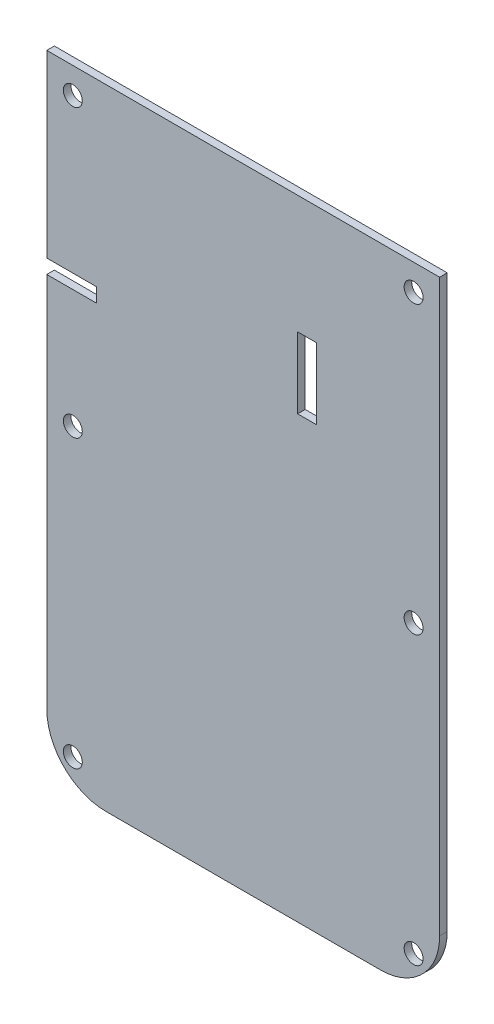
SolidWorks part; units mm, degrees
ref_plane "前视基准面" through (0, 0, 0) normal (0, 0, 1) x (1, 0, 0)
ref_plane "上视基准面" through (0, 0, 0) normal (0, 1, 0) x (1, 0, 0)
ref_plane "右视基准面" through (0, 0, 0) normal (1, 0, 0) x (0, 0, -1)
sketch "草图1" plane through (0, 0, 0) normal (0, 0, 1) x (1, 0, 0)
  line L1 (-41.5, 66.5) -> (0, 66.5)
  line L2 (-41.5, 66.5) -> (-41.5, 6.25)
  line L3 (-35.25, 0) -> (-6.25, 0)
  line L4 (0, 66.5) -> (0, 6.25)
  arc A0 (-6.25, 0) -> (0, 6.25) centre (-6.25, 6.25) ccw
  arc A1 (-35.25, 0) -> (-41.5, 6.25) centre (-35.25, 6.25) cw
  point P6 (0, 0)
  point P7 (0, 66.5)
  point P10 (-41.5, 66.5)
  point P13 (-41.5, 0)
  dimension "D3" = 6.25
  dimension "D1" = 41.5
  dimension "D2" = 66.5
extrude "凸台-拉伸1" add sketch "草图1" along normal blind 0.8 contours L2 A1 L3 A0 L4 L1
sketch "草图2" plane through (0, 0, 0.8) normal (0, 0, 1) x (1, 0, 0)
  line L0 (-41.5, 66.5) -> (-41.5, 6.25) construction
  line L1 (-41.5, 66.5) -> (0, 66.5) construction
  line L2 (-38.75, 63.75) -> (-38.75, 33.5) construction
  line L3 (-20.75, -943.2655) -> (-20.75, 49056.7345) construction
  line L4 (0, 66.5) -> (0, 6.25) construction
  line L11 (-41.5, 66.5) -> (-41.5, 6.25) construction
  line L12 (-41.5, 47.5) -> (-36.25, 47.5)
  line L13 (-41.5, 47.5) -> (-41.5, 46)
  line L14 (-41.5, 46) -> (-36.25, 46)
  line L15 (-36.25, 47.5) -> (-36.25, 46)
  line L16 (-41.5, 66.5) -> (0, 66.5) construction
  line L17 (0, 66.5) -> (0, 6.25) construction
  line L18 (-13, 54) -> (-15, 54)
  line L19 (-13, 54) -> (-13, 46.5)
  line L20 (-13, 46.5) -> (-15, 46.5)
  line L21 (-15, 54) -> (-15, 46.5)
  circle A0 centre (-38.75, 63.75) radius 1
  circle A1 centre (-38.75, 33.5) radius 1
  circle A2 centre (-38.75, 3.25) radius 1
  circle A3 centre (-2.75, 3.25) radius 1
  circle A4 centre (-2.75, 33.5) radius 1
  circle A5 centre (-2.75, 63.75) radius 1
  dimension "D1" = 2
  dimension "D2" = 2.75
  dimension "D3" = 2.75
  dimension "D5" = 30.25
  dimension "D6" = 5.25
  dimension "D7" = 1.5
  dimension "D8" = 19
  dimension "D9" = 2
  dimension "D10" = 7.5
  dimension "D11" = 12.5
  dimension "D12" = 13
  dimension "D4" = 3
extrude "切除-拉伸1" cut sketch "草图2" against normal through all
